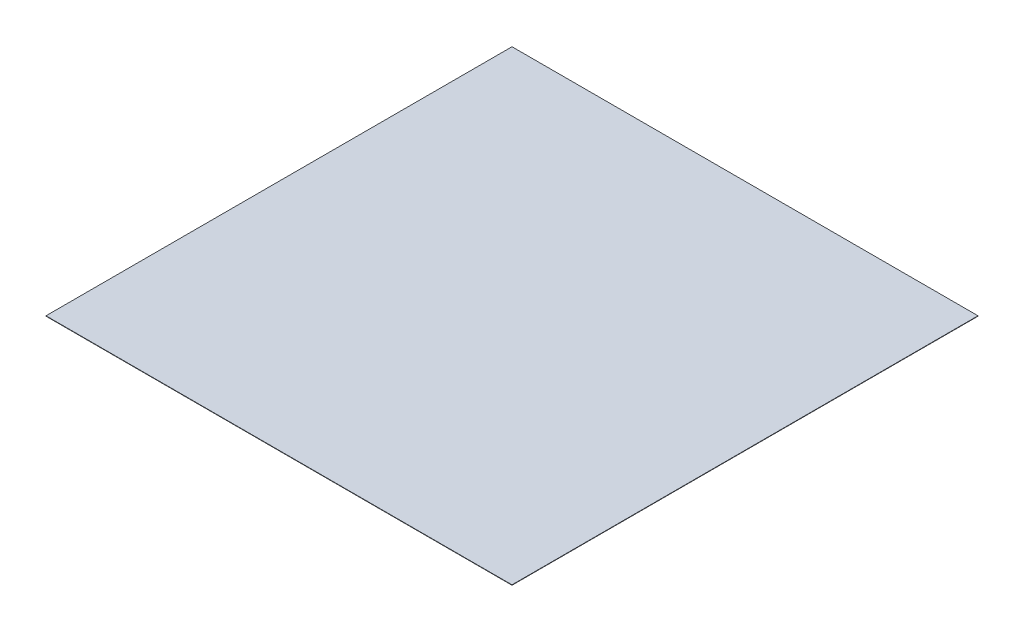
SolidWorks part; units mm, degrees
ref_plane "Front Plane" through (0, 0, 0) normal (0, 0, 1) x (1, 0, 0)
ref_plane "Top Plane" through (0, 0, 0) normal (0, 1, 0) x (1, 0, 0)
ref_plane "Right Plane" through (0, 0, 0) normal (1, 0, 0) x (0, 0, -1)
ref_plane "Plane1" through (0, 0, 134.8832) normal (0, 0, -1) x (-1, 0, 0)
sketch "Sketch2" plane through (0, 0, 134.8832) normal (0, 0, -1) x (-1, 0, 0)
  line L0 (-16.0101, 140.5644) -> (-16.0101, 106.5644)
  line L1 (-16.0101, 140.5644) -> (-16.0101, 106.5644) construction
  line L2 (-23.0101, 103.5644) -> (-19.0101, 103.5644)
  line L3 (-23.0101, 103.5644) -> (-19.0101, 103.5644) construction
  line L4 (-26.0101, 96.5644) -> (-26.0101, 100.5644)
  line L5 (-26.0101, 96.5644) -> (-26.0101, 100.5644) construction
  line L6 (-29.0101, 93.5644) -> (-63.0101, 93.5644)
  line L7 (-29.0101, 93.5644) -> (-63.0101, 93.5644) construction
  line L8 (-76.0101, 106.5644) -> (-76.0101, 140.5644)
  line L9 (-76.0101, 106.5644) -> (-76.0101, 140.5644) construction
  line L10 (-73.0101, 103.5644) -> (-69.0101, 103.5644)
  line L11 (-73.0101, 103.5644) -> (-69.0101, 103.5644) construction
  line L12 (-66.0101, 100.5644) -> (-66.0101, 96.5644)
  line L13 (-66.0101, 100.5644) -> (-66.0101, 96.5644) construction
  line L14 (-63.0101, 153.5644) -> (-29.0101, 153.5644)
  line L15 (-63.0101, 153.5644) -> (-29.0101, 153.5644) construction
  line L16 (-26.0101, 146.5644) -> (-26.0101, 150.5644)
  line L17 (-26.0101, 146.5644) -> (-26.0101, 150.5644) construction
  line L18 (-19.0101, 143.5644) -> (-23.0101, 143.5644)
  line L19 (-19.0101, 143.5644) -> (-23.0101, 143.5644) construction
  line L20 (-69.0101, 143.5644) -> (-73.0101, 143.5644)
  line L21 (-69.0101, 143.5644) -> (-73.0101, 143.5644) construction
  line L22 (-66.0101, 150.5644) -> (-66.0101, 146.5644)
  line L23 (-66.0101, 150.5644) -> (-66.0101, 146.5644) construction
  line L24 (-66.5101, 150.5644) -> (-66.5101, 146.5644)
  line L25 (-69.0101, 144.0644) -> (-73.0101, 144.0644)
  line L26 (-76.5101, 106.5644) -> (-76.5101, 140.5644)
  line L27 (-73.0101, 103.0644) -> (-69.0101, 103.0644)
  line L28 (-66.5101, 100.5644) -> (-66.5101, 96.5644)
  line L29 (-29.0101, 93.0644) -> (-63.0101, 93.0644)
  line L30 (-25.5101, 96.5644) -> (-25.5101, 100.5644)
  line L31 (-23.0101, 103.0644) -> (-19.0101, 103.0644)
  line L32 (-15.5101, 140.5644) -> (-15.5101, 106.5644)
  line L33 (-19.0101, 144.0644) -> (-23.0101, 144.0644)
  line L34 (-25.5101, 146.5644) -> (-25.5101, 150.5644)
  line L36 (-29.0101, 153.5644) -> (-84.0101, 153.5644)
  line L37 (-29.0101, 153.5644) -> (-8.0101, 153.5644)
  line L38 (-84.0101, 106.5644) -> (-84.0101, 140.5644)
  line L39 (-73.9683, 95.6063) -> (-73.9683, 95.6063)
  line L40 (-73.9683, 95.6063) -> (-73.9683, 95.6063)
  line L41 (-29.0101, 85.5644) -> (-63.0101, 85.5644)
  line L42 (-18.0519, 95.6063) -> (-18.0519, 95.6063)
  line L43 (-18.0519, 95.6063) -> (-18.0519, 95.6063)
  line L44 (-8.0101, 140.5644) -> (-8.0101, 106.5644)
  line L48 (-8.0101, 140.5644) -> (-8.0101, 153.5644)
  line L50 (-84.0101, 140.5644) -> (-84.0101, 153.5644)
  line L53 (-18.0519, 151.5226) -> (-18.0519, 151.5226) construction
  line L54 (-18.0519, 151.5226) -> (-18.0519, 151.5226) construction
  line L55 (-73.9683, 151.5226) -> (-73.9683, 151.5226) construction
  line L56 (-73.9683, 151.5226) -> (-73.9683, 151.5226) construction
  line L57 (-63.0101, 154.0644) -> (-29.0101, 154.0644) construction
  line L58 (-63.0101, 161.5644) -> (-29.0101, 161.5644) construction
  arc A0 (-19.0101, 103.5644) -> (-16.0101, 106.5644) centre (-19.0101, 106.5644) ccw
  arc A1 (-19.0101, 103.5644) -> (-16.0101, 106.5644) centre (-19.0101, 106.5644) ccw construction
  arc A2 (-23.0101, 103.5644) -> (-26.0101, 100.5644) centre (-23.0101, 100.5644) ccw
  arc A3 (-23.0101, 103.5644) -> (-26.0101, 100.5644) centre (-23.0101, 100.5644) ccw construction
  arc A4 (-29.0101, 93.5644) -> (-26.0101, 96.5644) centre (-29.0101, 96.5644) ccw
  arc A5 (-29.0101, 93.5644) -> (-26.0101, 96.5644) centre (-29.0101, 96.5644) ccw construction
  arc A6 (-66.0101, 96.5644) -> (-63.0101, 93.5644) centre (-63.0101, 96.5644) ccw
  arc A7 (-66.0101, 96.5644) -> (-63.0101, 93.5644) centre (-63.0101, 96.5644) ccw construction
  arc A8 (-76.0101, 106.5644) -> (-73.0101, 103.5644) centre (-73.0101, 106.5644) ccw
  arc A9 (-76.0101, 106.5644) -> (-73.0101, 103.5644) centre (-73.0101, 106.5644) ccw construction
  arc A10 (-66.0101, 100.5644) -> (-69.0101, 103.5644) centre (-69.0101, 100.5644) ccw
  arc A11 (-66.0101, 100.5644) -> (-69.0101, 103.5644) centre (-69.0101, 100.5644) ccw construction
  arc A12 (-26.0101, 150.5644) -> (-29.0101, 153.5644) centre (-29.0101, 150.5644) ccw
  arc A13 (-26.0101, 150.5644) -> (-29.0101, 153.5644) centre (-29.0101, 150.5644) ccw construction
  arc A14 (-26.0101, 146.5644) -> (-23.0101, 143.5644) centre (-23.0101, 146.5644) ccw
  arc A15 (-26.0101, 146.5644) -> (-23.0101, 143.5644) centre (-23.0101, 146.5644) ccw construction
  arc A16 (-16.0101, 140.5644) -> (-19.0101, 143.5644) centre (-19.0101, 140.5644) ccw
  arc A17 (-16.0101, 140.5644) -> (-19.0101, 143.5644) centre (-19.0101, 140.5644) ccw construction
  arc A18 (-63.0101, 153.5644) -> (-66.0101, 150.5644) centre (-63.0101, 150.5644) ccw
  arc A19 (-63.0101, 153.5644) -> (-66.0101, 150.5644) centre (-63.0101, 150.5644) ccw construction
  arc A20 (-69.0101, 143.5644) -> (-66.0101, 146.5644) centre (-69.0101, 146.5644) ccw
  arc A21 (-69.0101, 143.5644) -> (-66.0101, 146.5644) centre (-69.0101, 146.5644) ccw construction
  arc A22 (-73.0101, 143.5644) -> (-76.0101, 140.5644) centre (-73.0101, 140.5644) ccw
  arc A23 (-73.0101, 143.5644) -> (-76.0101, 140.5644) centre (-73.0101, 140.5644) ccw construction
  arc A24 (-69.0101, 144.0644) -> (-66.5101, 146.5644) centre (-69.0101, 146.5644) ccw
  arc A25 (-73.0101, 144.0644) -> (-76.5101, 140.5644) centre (-73.0101, 140.5644) ccw
  arc A26 (-76.5101, 106.5644) -> (-73.0101, 103.0644) centre (-73.0101, 106.5644) ccw
  arc A27 (-66.5101, 100.5644) -> (-69.0101, 103.0644) centre (-69.0101, 100.5644) ccw
  arc A28 (-66.5101, 96.5644) -> (-63.0101, 93.0644) centre (-63.0101, 96.5644) ccw
  arc A29 (-29.0101, 93.0644) -> (-25.5101, 96.5644) centre (-29.0101, 96.5644) ccw
  arc A30 (-23.0101, 103.0644) -> (-25.5101, 100.5644) centre (-23.0101, 100.5644) ccw
  arc A31 (-19.0101, 103.0644) -> (-15.5101, 106.5644) centre (-19.0101, 106.5644) ccw
  arc A32 (-15.5101, 140.5644) -> (-19.0101, 144.0644) centre (-19.0101, 140.5644) ccw
  arc A33 (-25.5101, 146.5644) -> (-23.0101, 144.0644) centre (-23.0101, 146.5644) ccw
  arc A34 (-25.5101, 150.5644) -> (-27.2073, 153.5644) centre (-29.0101, 150.5644) ccw
  arc A35 (-64.8129, 153.5644) -> (-66.5101, 150.5644) centre (-63.0101, 150.5644) ccw
  arc A37 (-63.0101, 154.0644) -> (-66.5101, 150.5644) centre (-63.0101, 150.5644) ccw construction
  arc A38 (-84.0101, 106.5644) -> (-73.9683, 95.6063) centre (-73.0101, 106.5644) ccw
  arc A39 (-73.9683, 95.6063) -> (-73.9683, 95.6063) centre (-73.9683, 95.6063) ccw
  arc A40 (-73.9683, 95.6063) -> (-63.0101, 85.5644) centre (-63.0101, 96.5644) ccw
  arc A41 (-29.0101, 85.5644) -> (-18.0519, 95.6063) centre (-29.0101, 96.5644) ccw
  arc A42 (-18.0519, 95.6063) -> (-18.0519, 95.6063) centre (-18.0519, 95.6063) ccw
  arc A43 (-18.0519, 95.6063) -> (-8.0101, 106.5644) centre (-19.0101, 106.5644) ccw
  arc A44 (-25.5101, 150.5644) -> (-29.0101, 154.0644) centre (-29.0101, 150.5644) ccw construction
  arc A49 (-8.0101, 140.5644) -> (-18.0519, 151.5226) centre (-19.0101, 140.5644) ccw construction
  arc A50 (-18.0519, 151.5226) -> (-29.0101, 161.5644) centre (-29.0101, 150.5644) ccw construction
  arc A51 (-63.0101, 161.5644) -> (-73.9683, 151.5226) centre (-63.0101, 150.5644) ccw construction
  arc A52 (-73.9683, 151.5226) -> (-84.0101, 140.5644) centre (-73.0101, 140.5644) ccw construction
  arc A53 (-18.0519, 151.5226) -> (-18.0519, 151.5226) centre (-18.0519, 151.5226) ccw construction
  arc A54 (-73.9683, 151.5226) -> (-73.9683, 151.5226) centre (-73.9683, 151.5226) ccw construction
  dimension "D1" = 0.5
  dimension "D2" = 8
extrude "Boss-Extrude1" add sketch "Sketch2" along normal blind 20 contours A41 A43 L44 L48 L37 A34 L34 A33 L33 A32 L32 A31 L31 A30 L30 A29 L29 A28 L28 A27 L27 A26 L26 A25 L25 A24 L24 A35 L36 L50 L38 A38 A40 L41 region at (17.6087, 152.5446, 134.8832)
ref_plane "Plane2" through (0, 153.5644, 0) normal (0, 1, 0) x (1, 0, 0)
sketch "Sketch3" plane through (0, 153.5644, 0) normal (0, 1, 0) x (1, 0, 0)
  line L1 (-1.9899, -144.8832) -> (24.2073, -144.8832)
  line L2 (-1.9899, -144.8832) -> (-1.9899, -104.8832)
  line L3 (-1.9899, -104.8832) -> (24.2073, -104.8832)
  line L4 (98.0101, -144.8832) -> (98.0101, -104.8832)
  line L5 (67.8129, -104.8832) -> (67.8129, -144.8832)
  line L7 (24.2073, -104.8832) -> (24.2073, -144.8832)
  line L9 (48.0101, -104.8832) -> (48.0101, -144.8832) construction
  line L10 (98.0101, -124.8832) -> (-1.9899, -124.8832) construction
  line L13 (67.8129, -104.8832) -> (98.0101, -104.8832)
  line L14 (67.8129, -144.8832) -> (98.0101, -144.8832)
  circle A0 centre (93.0101, -109.8832) radius 1.5
  circle A1 centre (93.0101, -139.8832) radius 1.5
  circle A2 centre (3.0101, -139.8832) radius 1.5
  circle A3 centre (3.0101, -109.8832) radius 1.5
  dimension "D5" = 67.8129
  dimension "D1" = 3
  dimension "D2" = 3.0101
  dimension "D3" = 24.2073
  dimension "D4" = 48.0101
  dimension "D6" = 93.0101
  dimension "D7" = 98.0101
  dimension "D8" = 1.9899
  dimension "D9" = 104.8832
  dimension "D10" = 109.8832
  dimension "D11" = 124.8832
  dimension "D12" = 139.8832
extrude "Boss-Extrude2" add sketch "Sketch3" along normal blind 5 from offset 5 offset against normal yes
ref_plane "Plane3" through (0, 223.5644, 0) normal (0, 1, 0) x (1, 0, 0)
sketch "Sketch4" plane through (0, 223.5644, 0) normal (0, 1, 0) x (1, 0, 0)
  line L0 (0, 0) -> (0, 600) construction
  line L1 (600, 600) -> (-600, 600)
  line L2 (600, 600) -> (600, -600)
  line L3 (600, -600) -> (-600, -600)
  line L4 (-600, 600) -> (-600, -600)
  line L5 (0, 0) -> (600, 0) construction
  dimension "D1" = 1200
  dimension "D2" = 1200
  dimension "D3" = 600
  dimension "D4" = 600
extrude "Boss-Extrude3" add sketch "Sketch4" along normal blind 1 separate body
